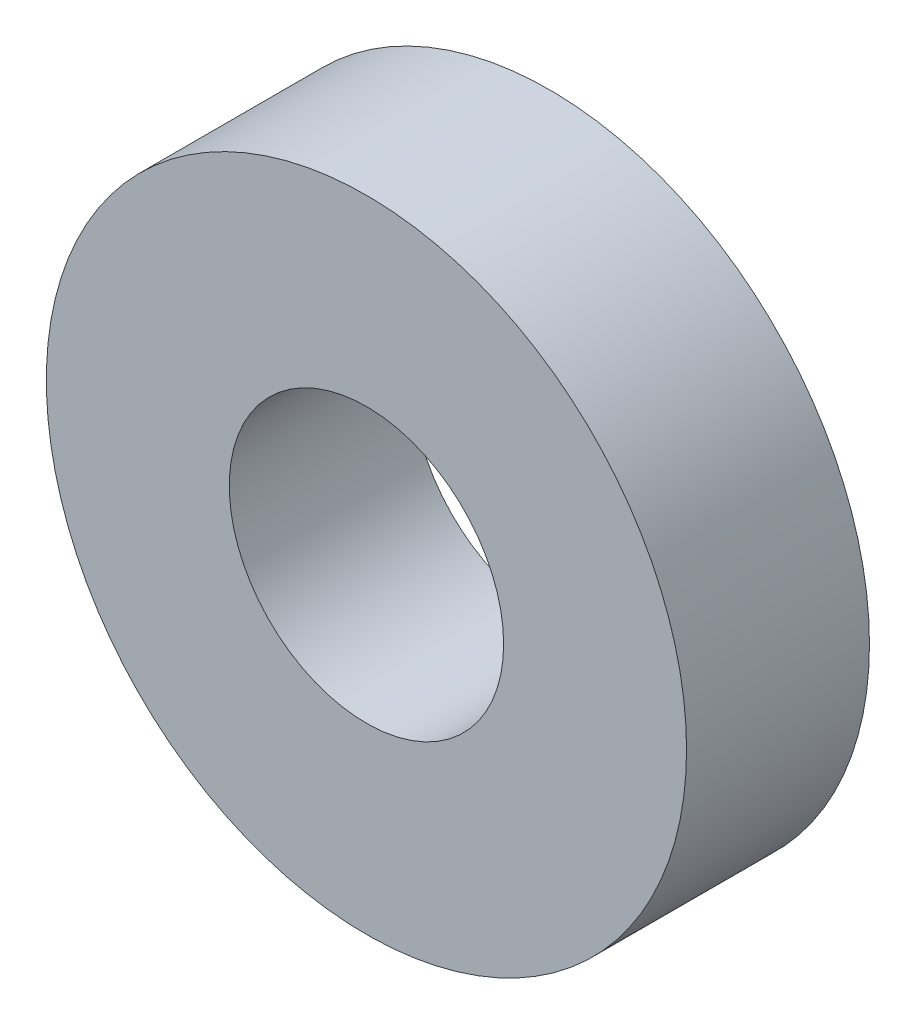
SolidWorks part; units mm, degrees
ref_plane "Front Plane" through (0, 0, 0) normal (0, 0, 1) x (1, 0, 0)
ref_plane "Top Plane" through (0, 0, 0) normal (0, 1, 0) x (1, 0, 0)
ref_plane "Right Plane" through (0, 0, 0) normal (1, 0, 0) x (0, 0, -1)
sketch "Sketch1" plane through (0, 0, 0) normal (0, 0, 1) x (1, 0, 0)
  circle A0 centre (0, 0) radius 6
  circle A1 centre (0, 0) radius 14
  dimension "D1" = 12
  dimension "D2" = 28
extrude "Boss-Extrude1" add sketch "Sketch1" along normal blind 4 and the other way blind 4
